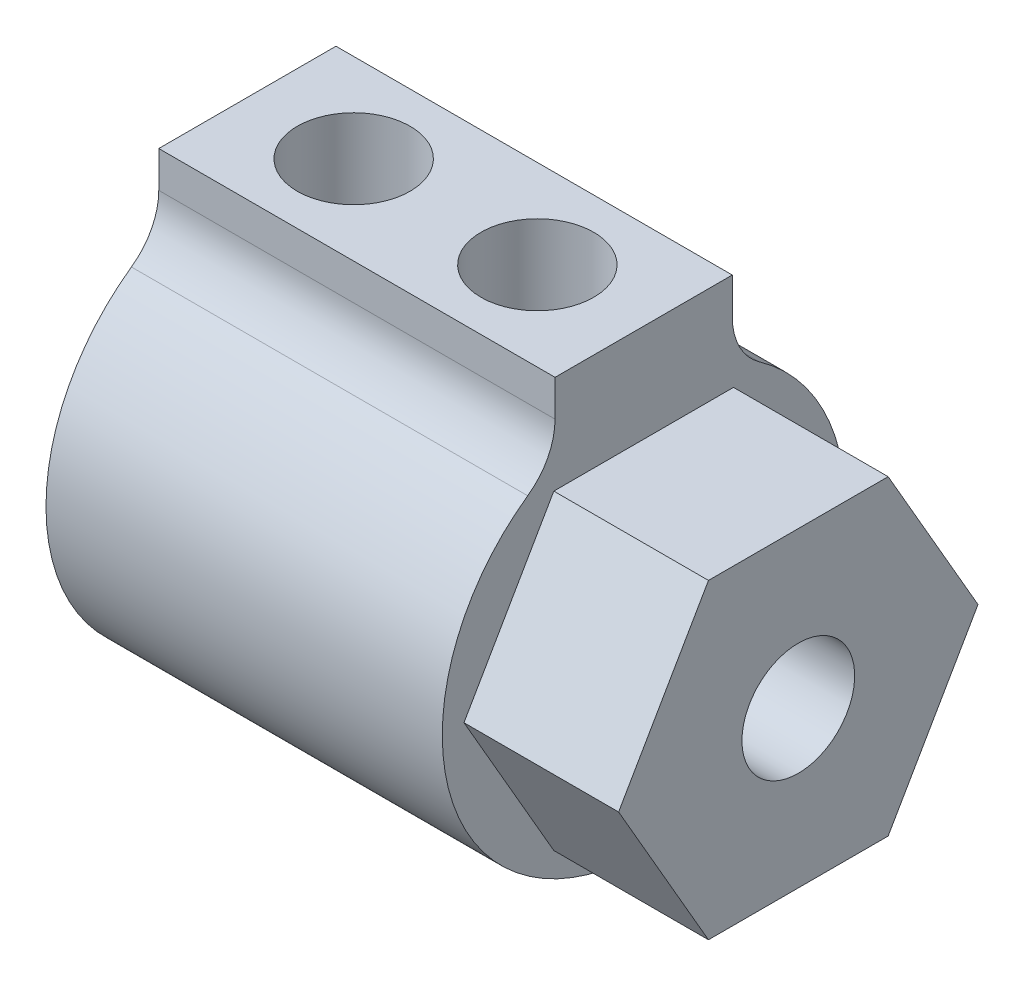
SolidWorks part; units mm, degrees
material "PLA2"
ref_plane "Front Plane" through (0, 0, 0) normal (0, 0, 1) x (1, 0, 0)
ref_plane "Top Plane" through (0, 0, 0) normal (0, 1, 0) x (1, 0, 0)
ref_plane "Right Plane" through (0, 0, 0) normal (1, 0, 0) x (0, 0, -1)
sketch "Sketch1" plane through (0, 0, 0) normal (1, 0, 0) x (0, 0, -1)
  line L0 (0, 0) -> (50000, 0) construction
  line L1 (-3.5415, 6.1341) -> (3.5415, 6.1341)
  line L2 (3.5415, 6.1341) -> (7.083, 0)
  line L3 (0, 0) -> (0, 50000) construction
  line L4 (-3.5415, 6.1341) -> (-7.083, 0)
  line L5 (-3.5415, -6.1341) -> (-7.083, 0)
  line L6 (3.5415, -6.1341) -> (7.083, 0)
  line L7 (-3.5415, -6.1341) -> (3.5415, -6.1341)
  point P8 (0, 6.1341)
  point P13 (0, -6.1341)
  dimension "D1" = 12.2682
  dimension "D2" = 12.2682
extrude "Hex" add sketch "Sketch1" along normal blind 6.096
sketch "Sketch2" plane through (0, 0, 0) normal (-1, 0, 0) x (0, 0, 1)
  line L0 (1.6637, 2.8081) -> (-1.6637, 2.8081)
  circle A0 centre (0, 0) radius 7.9375
  arc A1 (-1.6637, 2.8081) -> (1.6637, 2.8081) centre (0, 0) ccw
  dimension "D1" = 6.5278
  dimension "D2" = 15.875
  dimension "D3" = 3.3274
extrude "Rotary_Shaft" add sketch "Sketch2" along normal blind 15.621
sketch "Sketch5" plane through (-15.621, 0, 0) normal (-1, 0, 0) x (0, 0, 1)
  line L0 (0, 0) -> (0, 50000) construction
  line L1 (-3.4925, 7.1279) -> (-3.4925, 9.9949)
  line L2 (-3.4925, 9.9949) -> (3.4925, 9.9949)
  line L3 (3.4925, 7.1279) -> (3.4925, 9.9949)
  line L4 (0, 3.2639) -> (50000, 3.2639) construction
  arc A0 (3.4925, 7.1279) -> (-3.4925, 7.1279) centre (0, 0) ccw
  circle A1 centre (0, 0) radius 7.9375 construction
  circle A4 centre (0, 0) radius 3.2639 construction
  point P9 (0, 9.9949)
  dimension "D1" = 6.985
  dimension "D2" = 6.731
extrude "Boss-Extrude1" add sketch "Sketch5" against normal up to surface (15.621 mm away) up to face at (0, 0, 7.9375)
sketch "Sketch3" plane through (0, 0, 0) normal (0, 1, 0) x (1, 0, 0)
  line L0 (-15.621, -7.9375) -> (0, -7.9375) construction
  line L1 (-15.621, 7.9375) -> (-15.621, -7.9375) construction
  line L2 (0, 7.9375) -> (-15.621, 7.9375) construction
  line L3 (-15.621, -7.9375) -> (0, -7.9375) construction
  line L4 (-15.621, 7.9375) -> (-15.621, -7.9375) construction
  line L5 (0, 7.9375) -> (-15.621, 7.9375) construction
  line L6 (-15.621, 0) -> (0, 0) construction
  circle A0 centre (-11.43, 0) radius 2.2225
  circle A1 centre (-4.191, 0) radius 2.2225
  dimension "D1" = 4.445
  dimension "D2" = 4.445
  dimension "D3" = 4.191
  dimension "D4" = 7.239
extrude "Shaft-SetScrew-Holes" cut sketch "Sketch3" along normal through all
sketch "Sketch4" plane through (0, 0, 0) normal (-1, 0, 0) x (0, 0, 1)
  circle A0 centre (0, 0) radius 2.2225
  dimension "D1" = 4.445
extrude "Cut-Extrude2" cut sketch "Sketch4" against normal through all
fillet "Fillet1" radius 2.54 2 edges at (-7.8105, 7.1279, 3.4925) (-7.8105, 7.1279, -3.4925)
fillet "Fillet2" radius 0.381 6 edges at (-1.3587, 2.8081, -1.6637) (-1.3587, 2.8081, 1.6637) (-7.8105, 2.8081, 1.6637) (-7.8105, 2.8081, -1.6637) (-14.2623, 2.8081, 1.6637) (-14.2623, 2.8081, -1.6637)
equation "\"D2@Sketch3\"=\"D1@Sketch3\""
equation "\"D2@Sketch1\"=\"D1@Sketch1\""
